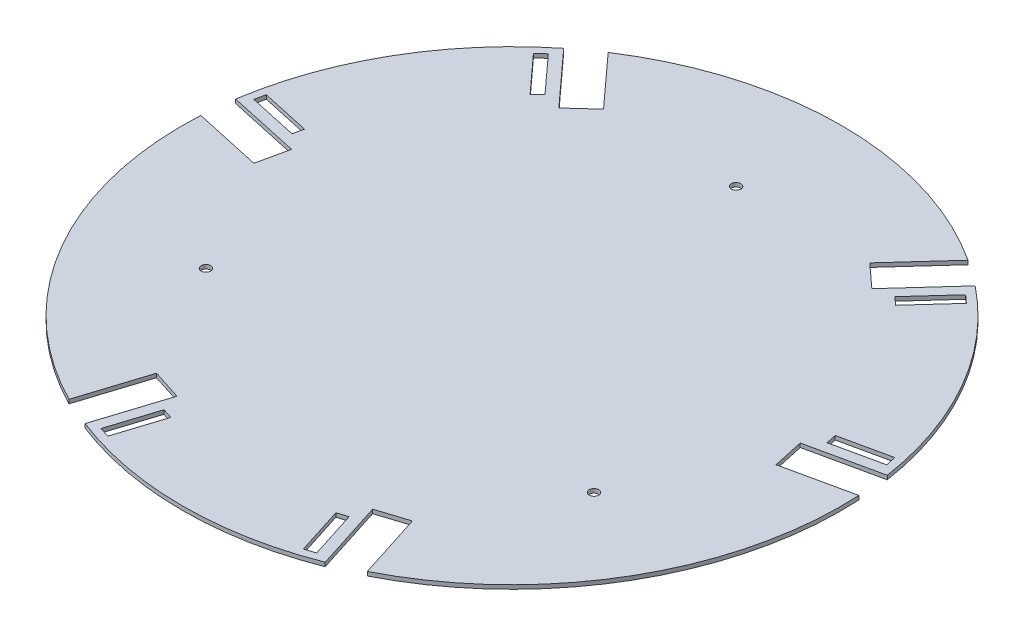
SolidWorks part; units mm, degrees
ref_plane "Front Plane" through (0, 0, 0) normal (0, 0, 1) x (1, 0, 0)
ref_plane "Top Plane" through (0, 0, 0) normal (0, 1, 0) x (1, 0, 0)
ref_plane "Right Plane" through (0, 0, 0) normal (1, 0, 0) x (0, 0, -1)
sketch "Sketch2" plane through (0, 0, 0) normal (0, 1, 0) x (1, 0, 0)
  circle A0 centre (0, 0) radius 125
  dimension "D1" = 250
extrude "Boss-Extrude1" add sketch "Sketch2" along normal blind 1.5 contours A0
sketch "Sketch3" plane through (0, 1.5, 0) normal (0, 1, 0) x (1, 0, 0)
  line L0 (0, 0) -> (-38, -119.084) construction
  line L1 (-270.1917, -358.6733) -> (-267.1917, -358.6733)
  line L2 (-270.1917, -358.6733) -> (-270.1917, -377.6733)
  line L3 (-270.1917, -377.6733) -> (-267.1917, -377.6733)
  line L4 (-267.1917, -358.6733) -> (-267.1917, -377.6733)
  line L9 (-38, -119.084) -> (38, -119.084) construction
  line L10 (0, 0) -> (0, -293.8403) construction
  line L11 (31.312, -98.1252) -> (35.1227, -96.9092)
  line L12 (37.088, -116.226) -> (40.8987, -115.01)
  line L14 (37.088, -116.226) -> (31.312, -98.1252)
  line L15 (40.8987, -115.01) -> (35.1227, -96.9092)
  line L17 (-38, -119.084) -> (-37.088, -116.226) construction
  line L19 (-37.088, -116.226) -> (-31.312, -98.1252)
  line L20 (-37.088, -116.226) -> (-40.8987, -115.01)
  line L21 (-31.312, -98.1252) -> (-35.1227, -96.9092)
  line L22 (-40.8987, -115.01) -> (-35.1227, -96.9092)
  line L52 (-82.1107, 90.2321) -> (-69.3229, 76.1796)
  line L53 (-82.1107, 90.2321) -> (-79.1522, 92.9243)
  line L54 (-79.1522, 92.9243) -> (-66.3645, 78.8717)
  line L55 (-69.3229, 76.1796) -> (-66.3645, 78.8717)
  line L56 (-100.6349, 21.9456) -> (-101.4872, 18.0375)
  line L57 (-120.0509, 22.0857) -> (-101.4872, 18.0375)
  line L58 (-119.1987, 25.9938) -> (-120.0509, 22.0857)
  line L59 (-119.1987, 25.9938) -> (-100.6349, 21.9456)
  line L60 (119.1987, 25.9938) -> (100.6349, 21.9456)
  line L61 (119.1987, 25.9938) -> (120.0509, 22.0857)
  line L62 (120.0509, 22.0857) -> (101.4872, 18.0375)
  line L63 (100.6349, 21.9456) -> (101.4872, 18.0375)
  line L64 (69.3229, 76.1796) -> (66.3645, 78.8717)
  line L65 (79.1522, 92.9243) -> (66.3645, 78.8717)
  line L66 (82.1107, 90.2321) -> (79.1522, 92.9243)
  line L67 (82.1107, 90.2321) -> (69.3229, 76.1796)
  circle A1 centre (0, 0) radius 125 construction
  point P18 (0, 0)
  point P38 (-15.7426, 25.0605)
  point P39 (0, 0)
  point P46 (-7.6333, 12.5317)
  dimension "D1" = 3
  dimension "D2" = 19
  dimension "D3" = 76
  dimension "D4" = 3
  dimension "D5" = 3
  dimension "D7" = 4
  dimension "D8" = 19
extrude "Cut-Extrude1" cut sketch "Sketch3" against normal through all
sketch "Sketch4" plane through (0, 1.5, 0) normal (0, 1, 0) x (1, 0, 0)
  circle A3 centre (0, 85) radius 1.8
  circle A4 centre (73.6122, -42.5) radius 1.8
  circle A5 centre (-73.6122, -42.5) radius 1.8
  point P8 (0, 0)
  dimension "D1" = 85
  dimension "D2" = 3
  dimension "D3" = 3.6
extrude "Cut-Extrude2" cut sketch "Sketch4" against normal through all
sketch "Sketch6" plane through (0, 1.5, 0) normal (0, 1, 0) x (1, 0, 0)
  line L0 (-40.8987, -115.01) -> (-44.7094, -113.794) construction
  line L1 (-35.1227, -96.9092) -> (-40.8987, -115.01) construction
  line L2 (0, 0) -> (0, -140.3527) construction
  line L3 (-44.7094, -113.794) -> (-55.9925, -149.153) construction
  line L4 (-55.9925, -149.153) -> (-67.4246, -145.505)
  line L5 (-55.9925, -149.153) -> (-37.1094, -89.9772)
  line L6 (-67.4246, -145.505) -> (-48.5414, -86.3292)
  line L7 (-37.1094, -89.9772) -> (-48.5414, -86.3292)
  line L8 (67.4246, -145.505) -> (48.5414, -86.3292)
  line L9 (37.1094, -89.9772) -> (48.5414, -86.3292)
  line L10 (55.9925, -149.153) -> (37.1094, -89.9772)
  line L11 (55.9925, -149.153) -> (67.4246, -145.505)
  dimension "D1" = 12
  dimension "D2" = 25
  dimension "D3" = 4
extrude "Cut-Extrude5" cut sketch "Sketch6" against normal through all
pattern_circular "CirPattern2" count 3 over 360 about axis through (0, 1.5, 0) along (0, 1, 0) of "Cut-Extrude5"
sketch "Sketch7" [suppressed] plane through (0, 1.5, 0) normal (0, 1, 0) x (1, 0, 0)
  line L2 (124.8177, 6.7492) -> (-0.2769, 0.4642)
  line L3 (-0.2769, 0.4642) -> (56.5639, -111.4698)
  line L4 (56.5639, -111.4698) -> (48.5414, -86.3292) construction
  arc A0 (56.5639, -111.4698) -> (124.8177, 6.7492) centre (0, 0) ccw construction
  arc A1 (56.5639, -111.4698) -> (124.8177, 6.7492) centre (0, 0) ccw
  dimension "D2" = 9.224
  dimension "D1" = 65.954
